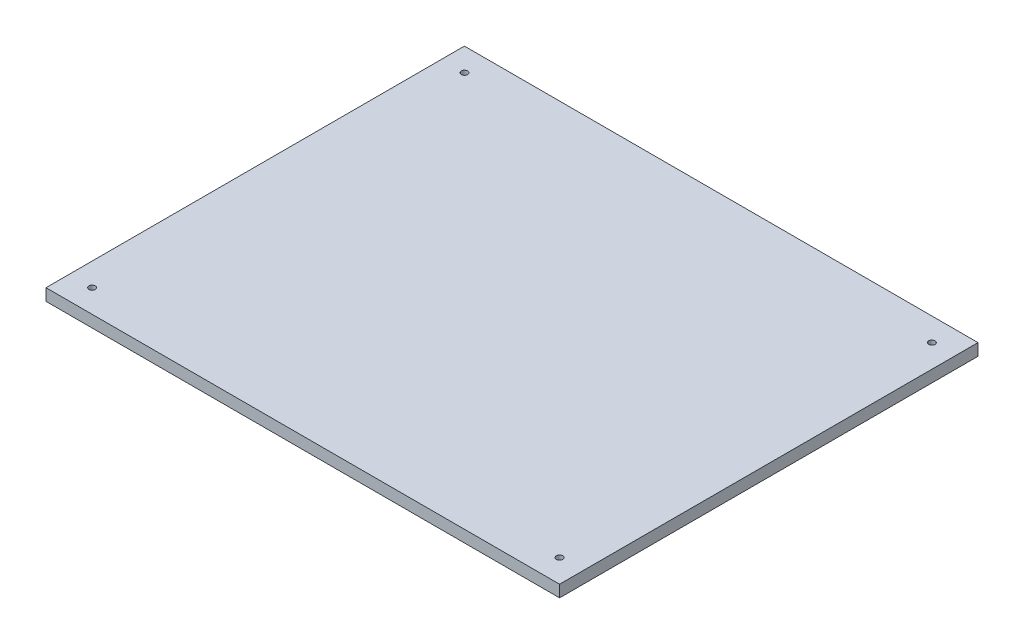
SolidWorks part; units mm, degrees
material "Acrylic (Medium-high impact)"
ref_plane "Front Plane" through (0, 0, 0) normal (0, 0, 1) x (1, 0, 0)
ref_plane "Top Plane" through (0, 0, 0) normal (0, 1, 0) x (1, 0, 0)
ref_plane "Right Plane" through (0, 0, 0) normal (1, 0, 0) x (0, 0, -1)
sketch "Sketch1" plane through (0, 0, 0) normal (0, 1, 0) x (1, 0, 0)
  line L1 (-137.3886, 111.9378) -> (137.3886, 111.9378)
  line L2 (-137.3886, 111.9378) -> (-137.3886, -111.9378)
  line L3 (-137.3886, -111.9378) -> (137.3886, -111.9378)
  line L4 (137.3886, 111.9378) -> (137.3886, -111.9378)
  line L5 (-137.3886, 111.9378) -> (137.3886, -111.9378) construction
  line L6 (-137.3886, -111.9378) -> (137.3886, 111.9378) construction
  point P0 (0, 0)
  dimension "D1" = 223.8756
  dimension "D2" = 274.7772
extrude "Boss-Extrude1" add sketch "Sketch1" along normal blind 6.35
hole_wizard "M3 Clearance Hole1" positions "Sketch2" profile "Sketch3" hole size "M3" standard "ANSI Metric" end condition through all
sketch "Sketch2" plane through (0, 6.35, 0) normal (0, 1, 0) x (1, 0, 0)
  line L0 (-137.3886, -111.9378) -> (137.3886, -111.9378) construction
  line L1 (137.3886, -111.9378) -> (137.3886, 111.9378) construction
  line L2 (137.3886, 111.9378) -> (-137.3886, 111.9378) construction
  line L3 (-137.3886, 111.9378) -> (-137.3886, -111.9378) construction
  point P0 (125.0442, -99.5934)
  point P2 (-125.0442, -99.5934)
  point P4 (-125.0442, 99.5934)
  point P6 (125.0442, 99.5934)
  dimension "D1" = 12.3444
  dimension "D2" = 12.3444
  dimension "D3" = 12.3444
  dimension "D4" = 12.3444
sketch "Sketch3" plane through (125.0442, 6.35, 99.5934) normal (1, 0, 0) x (0, 0, 1)
  line L0 (0, 0) -> (0, 6.35)
  line L1 (0, 6.35) -> (1.7, 6.35)
  line L2 (1.7, 6.35) -> (1.7, 0)
  line L5 (1.7, 0) -> (0, 0)
  line L11 (0, -6.35) -> (0, 107.95) construction
  dimension "Thru Hole Dia." = 3.4
  dimension "Thru Hole Depth" = 6.35
